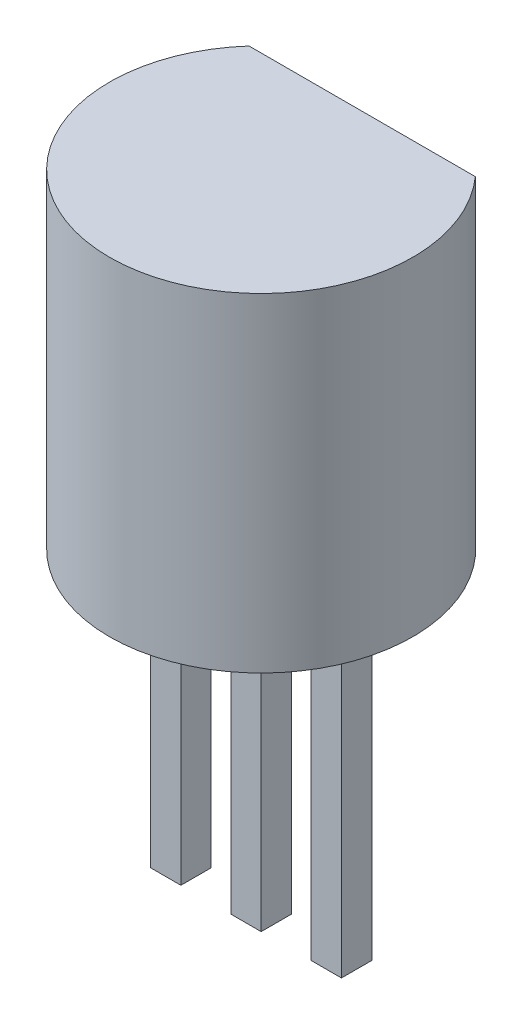
SolidWorks part; units mm, degrees
ref_plane "Alzado" through (0, 0, 0) normal (0, 0, 1) x (1, 0, 0)
ref_plane "Planta" through (0, 0, 0) normal (0, 1, 0) x (1, 0, 0)
ref_plane "Vista lateral" through (0, 0, 0) normal (1, 0, 0) x (0, 0, -1)
sketch "Sketch1" plane through (0, 0, 0) normal (0, 1, 0) x (1, 0, 0)
  line L0 (-1.79, 1.5987) -> (1.79, 1.5987)
  arc A0 (-1.79, 1.5987) -> (1.79, 1.5987) centre (0, 0) ccw
  dimension "D1" = 4.8
  dimension "D2" = 3.58
extrude "Boss-Extrude1" add sketch "Sketch1" along normal blind 5.2
sketch "Sketch2" plane through (0, 0, 0) normal (0, -1, 0) x (1, 0, 0)
  line L0 (-0.24, 0.24) -> (0.24, -0.24) construction
  line L5 (-0.24, 0.24) -> (0.24, 0.24)
  line L6 (-0.24, 0.24) -> (-0.24, -0.24)
  line L7 (-0.24, -0.24) -> (0.24, -0.24)
  line L8 (0.24, 0.24) -> (0.24, -0.24)
  point P0 (0, 0)
  dimension "D1" = 0.48
extrude "Boss-Extrude2" add sketch "Sketch2" along normal blind 5
pattern_linear "LPattern1" count 2 spacing 1.27 along (1, 0, 0) count 2 spacing 1.27 along (-1, 0, 0) of "Boss-Extrude2" pattern seed only yes
ref_axis "Axis1" through (0, 5.71, 0) along (0, -1, 0)
